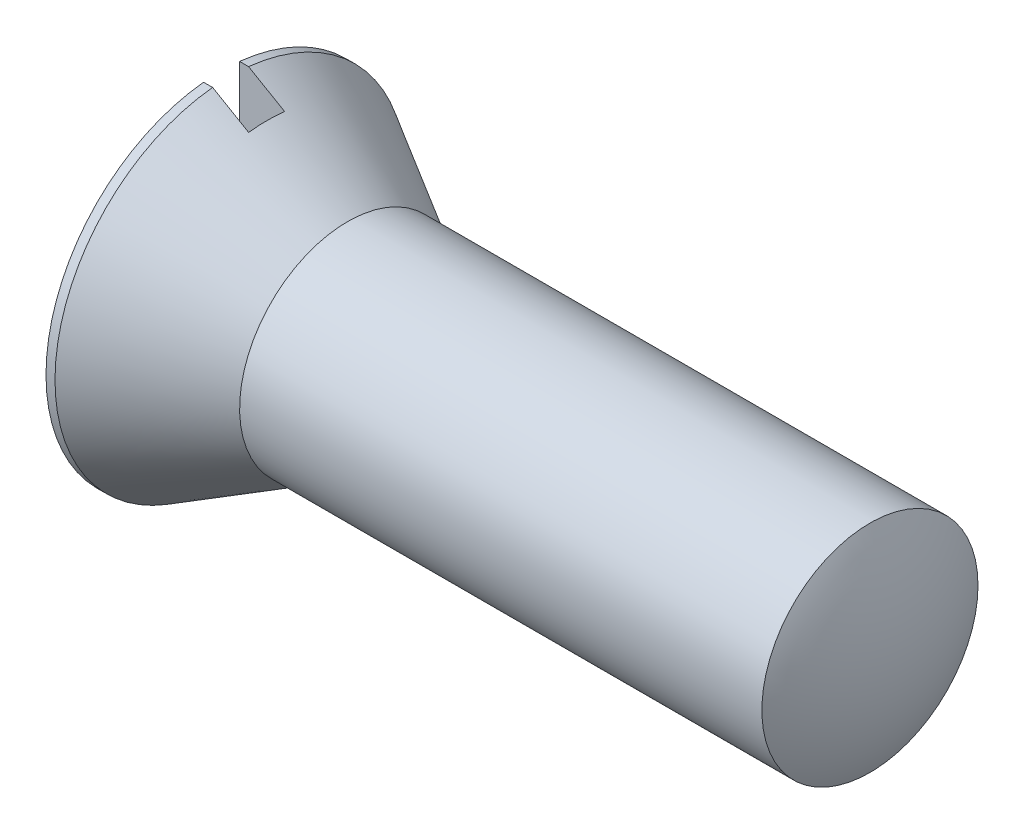
SolidWorks part; units mm, degrees
ref_plane "Front Plane" through (0, 0, 0) normal (0, 0, 1) x (1, 0, 0)
ref_plane "Top Plane" through (0, 0, 0) normal (0, 1, 0) x (1, 0, 0)
ref_plane "Right Plane" through (0, 0, 0) normal (1, 0, 0) x (0, 0, -1)
sketch "BaseBodySke" plane through (0, 0, 0) normal (0, 0, 1) x (1, 0, 0)
  line L0 (-107.4075, 0) -> (214.0904, 0) construction
  line L1 (0, 0) -> (0, 19.5)
  line L2 (0, 19.5) -> (1, 19.5)
  line L3 (1, 19.5) -> (14, 12)
  line L4 (14, 12) -> (75, 12)
  line L5 (75, 12) -> (75, 0)
  line L6 (75, 0) -> (0, 0)
  line L7 (21, 10) -> (21, -17.9005) construction
  line L8 (34.0602, 10.8985) -> (57.5082, 10.8985) construction
  line L9 (73, 13.8049) -> (73, -14.5195) construction
  dimension "Thread_length" = 54
  dimension "Length" = 75
revolve "BaseBody" add sketch "BaseBodySke" angle 360 about L6
cosmetic thread "ThreadCosmetic" [suppressed] parameters "Thread_length"=54, "Thread_minor"=21.797
sketch "FlatEndSke" plane through (0, 0, 0) normal (0, 0, 1) x (1, 0, 0)
  line L0 (72, 12) -> (75, 12)
  line L1 (75, 12) -> (75, 9)
  line L2 (75, 9) -> (72, 12)
  line L3 (75, -12) -> (75, 12) construction
  line L4 (75, 12) -> (14, 12) construction
  line L5 (0, 0) -> (89.7899, 0) construction
  dimension "D1" = 45
revolve "FlatEnd" [suppressed] cut sketch "FlatEndSke" angle 360 about L5
sketch "CutEndSke" plane through (75, 0, 0) normal (1, 0, 0) x (0, 0, -1)
  circle A0 centre (0, 0) radius 12 construction
  circle A1 centre (0, 0) radius 12
extrude "CutEnd" cut sketch "CutEndSke" against normal blind 3
dome "RoundEnd" faces to dome 1 distance 3 reverse direction no elliptical dome no face at (72, 0, -12) parameters "D1"=3
sketch "CutSlotSke" plane through (0, 0, 0) normal (0, 1, 0) x (1, 0, 0)
  line L0 (0, 0) -> (55.4791, 0) construction
  line L1 (0, 2) -> (5, 2)
  line L2 (0, 2) -> (0, -2)
  line L3 (0, -2) -> (5, -2)
  line L4 (5, 2) -> (5, -2)
  dimension "Slot_width" = 4
  dimension "Slot_depth" = 5
extrude "CutSlot" cut sketch "CutSlotSke" against normal mid plane 41
sketch "ThdSchSke" plane through (0, 0, 0) normal (0, 0, 1) x (1, 0, 0)
  line L0 (0, 0) -> (89.8666, 0) construction
  line L1 (75, -27.1828) -> (75, 30.5493) construction
  line L2 (71.4, 10.8985) -> (70.764, 12)
  line L3 (70.764, 12) -> (70.764, 13.2719)
  line L4 (70.764, 13.2719) -> (72.036, 13.2719)
  line L5 (72.036, 13.2719) -> (72.036, 12)
  line L6 (72.036, 12) -> (71.4, 10.8985)
  dimension "Length" = 75
  dimension "Advance" = 3.6
  dimension "D1" = 21.797
  dimension "D2" = 24
revolve "ThreadSchematic" [suppressed] cut sketch "ThdSchSke" angle 360 about L0
pattern_linear "ThdSchPat" [suppressed] count 27 spacing 2 along (-1, 0, 0) of bodies 105
equation "\"Thread_minor@ThreadCosmetic\" = \"Minor_dia@BaseBodySke\""
equation "\"Thread_length@ThreadCosmetic\" = \"Thread_length@BaseBodySke\""
equation "\"D1@CutEnd\" = \"Chamfer_width@FlatEndSke\""
equation "\"D1@RoundEnd\" = \"Chamfer_width@FlatEndSke\""
equation "\"D1@CutSlot\" = \"Head_diameter@BaseBodySke\"+2"
equation "\"Length@ThdSchSke\" = \"Length@BaseBodySke\""
equation "\"Advance@ThdSchSke\" = \"Advance@BaseBodySke\"*1.8"
equation "\"D2@ThdSchSke\" = \"Diameter@BaseBodySke\""
equation "\"D1@ThdSchSke\" = \"Minor_dia@BaseBodySke\""
equation "\"D3@ThdSchPat\" = \"Advance@BaseBodySke\""
equation "\"D1@ThdSchPat\" =  int( \"Thread_length@BaseBodySke\" / \"Advance@BaseBodySke\" ) "
